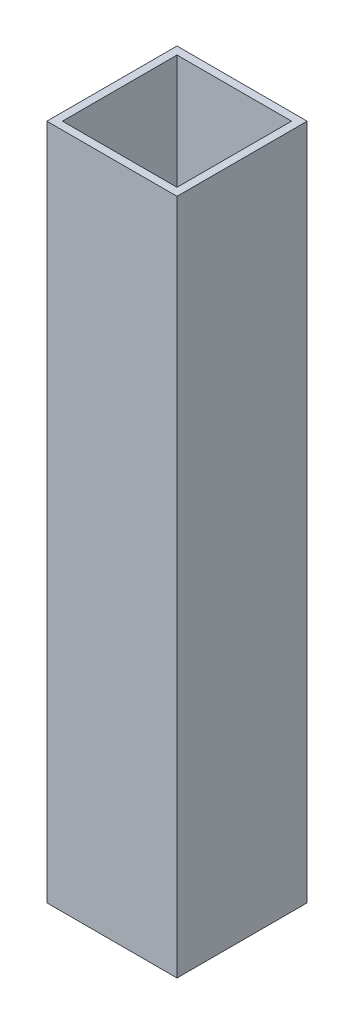
SolidWorks part; units mm, degrees
material "1060 Alloy"
ref_plane "Front Plane" through (0, 0, 0) normal (0, 0, 1) x (1, 0, 0)
ref_plane "Top Plane" through (0, 0, 0) normal (0, 1, 0) x (1, 0, 0)
ref_plane "Right Plane" through (0, 0, 0) normal (1, 0, 0) x (0, 0, -1)
sketch "Sketch1" plane through (0, 0, 0) normal (0, 1, 0) x (1, 0, 0)
  line L0 (0, 63.6278) -> (0, -69.3975) construction
  line L1 (-105.4586, 0) -> (105.4586, 0) construction
  line L2 (-11, 11) -> (-11, -11)
  line L3 (-12.5, 12.5) -> (12.5, 12.5)
  line L4 (-12.5, 12.5) -> (-12.5, -12.5)
  line L5 (-12.5, -12.5) -> (12.5, -12.5)
  line L6 (12.5, 12.5) -> (12.5, -12.5)
  line L7 (-11, -11) -> (11, -11)
  line L8 (11, 11) -> (11, -11)
  line L13 (-11, 11) -> (11, 11)
  point P5 (0, 0)
  dimension "D1" = 25
  dimension "D2" = 25
  dimension "D3" = 0
  dimension "D4" = 1.5
  dimension "D5" = 11
  dimension "D6" = 11
extrude "Boss-Extrude1" add sketch "Sketch1" along normal blind 65 and the other way blind 65
